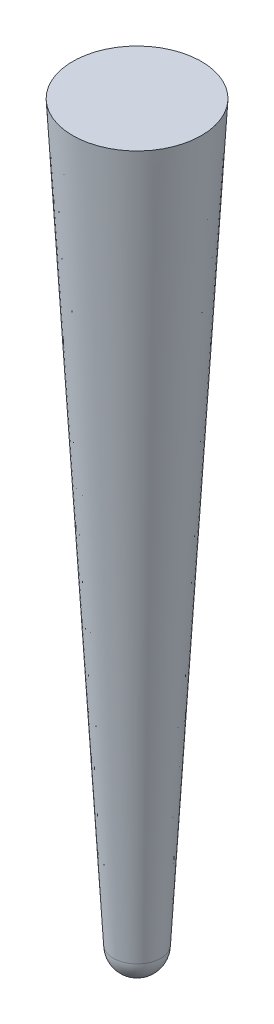
SolidWorks part; units mm, degrees
ref_plane "Front Plane" through (0, 0, 0) normal (0, 0, 1) x (1, 0, 0)
ref_plane "Top Plane" through (0, 0, 0) normal (0, 1, 0) x (1, 0, 0)
ref_plane "Right Plane" through (0, 0, 0) normal (1, 0, 0) x (0, 0, -1)
sketch "Sketch1" plane through (0, 0, 0) normal (0, 0, 1) x (1, 0, 0)
  line L0 (-21.59, 29.7328) -> (21.59, 29.7328)
  line L1 (-7.9375, -216.3297) -> (7.9375, -216.3297)
  line L2 (-21.59, 29.7328) -> (-7.9375, -216.3297)
  line L3 (21.59, 29.7328) -> (7.9375, -216.3297)
  line L4 (0, -224.2672) -> (0, 29.7328) construction
  arc A0 (-7.9375, -216.3297) -> (7.9375, -216.3297) centre (0, -216.3297) ccw
  point P2 (0, 29.7328)
  point P5 (0, -216.3297)
  point P8 (0, -216.3297)
  point P9 (0, -224.2672)
  dimension "D1" = 43.18
  dimension "D3" = 15.875
  dimension "D4" = 254
revolve "Revolve1" add sketch "Sketch1" angle 360 about L4 region at (7.9079, -74.3366, 0) region at (3.3688, -219.6985, 0)
